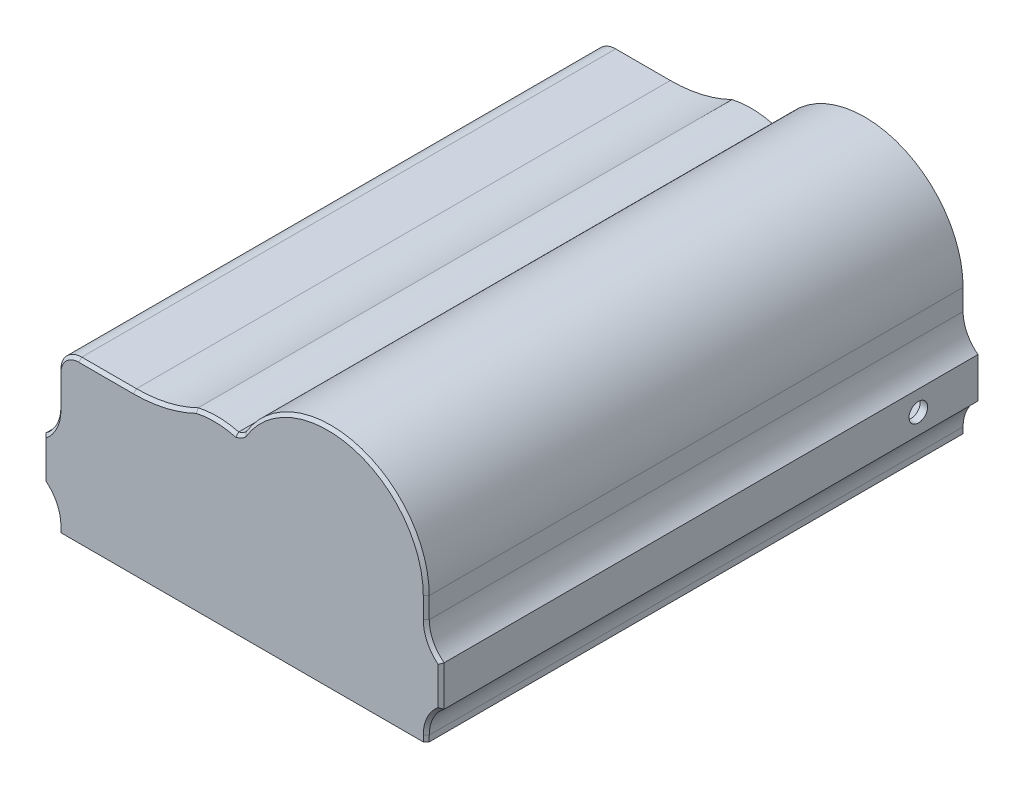
SolidWorks part; units mm, degrees
material "Nylon 6/10"
ref_plane "Front Plane" through (0, 0, 0) normal (0, 0, 1) x (1, 0, 0)
ref_plane "Top Plane" through (0, 0, 0) normal (0, 1, 0) x (1, 0, 0)
ref_plane "Right Plane" through (0, 0, 0) normal (1, 0, 0) x (0, 0, -1)
sketch "Sketch1" plane through (0, 0, -195.5168) normal (0, 0, 1) x (1, 0, 0)
  line L7 (104.3078, -30.7874) -> (104.3078, -41.7094) construction
  line L8 (107.547, -28.7554) -> (106.3398, -28.7554) construction
  line L9 (113.7687, -28.7554) -> (107.547, -28.7554) construction
  line L16 (115.6581, -28.7554) -> (113.7687, -28.7554) construction
  line L17 (163.9978, -41.7094) -> (163.9978, -32.8194) construction
  line L18 (163.9978, -42.9794) -> (163.9978, -41.7094) construction
  line L19 (163.9978, -42.9794) -> (166.5378, -42.9794) construction
  line L20 (166.5378, -42.9794) -> (166.5378, -46.7894) construction
  line L21 (166.5378, -46.7894) -> (163.9978, -46.7894) construction
  line L22 (163.9978, -49.3294) -> (163.9978, -46.7894) construction
  line L23 (163.9978, -49.3294) -> (104.3078, -49.3294) construction
  line L24 (104.3078, -49.3294) -> (104.3078, -46.7894) construction
  line L25 (104.3078, -46.7894) -> (101.7678, -46.7894) construction
  line L26 (101.7678, -46.7894) -> (101.7678, -42.9794) construction
  line L27 (101.7678, -42.9794) -> (104.3078, -42.9794) construction
  line L28 (104.3078, -42.9794) -> (104.3078, -41.7094) construction
  line L29 (104.3078, -30.7874) -> (104.3078, -41.7094) construction
  line L30 (107.547, -28.7554) -> (106.3398, -28.7554) construction
  line L31 (113.7687, -28.7554) -> (107.547, -28.7554) construction
  line L32 (115.6581, -28.7554) -> (113.7687, -28.7554) construction
  line L33 (163.9978, -41.7094) -> (163.9978, -32.8194) construction
  line L35 (163.9978, -42.9794) -> (163.9978, -41.7094) construction
  line L36 (163.9978, -42.9794) -> (166.5378, -42.9794) construction
  line L37 (166.5378, -42.9794) -> (166.5378, -46.7894) construction
  line L38 (166.5378, -46.7894) -> (163.9978, -46.7894) construction
  line L39 (163.9978, -49.3294) -> (163.9978, -46.7894) construction
  line L40 (163.9978, -49.3294) -> (104.3078, -49.3294) construction
  line L41 (104.3078, -49.3294) -> (104.3078, -46.7894) construction
  line L42 (104.3078, -46.7894) -> (101.7678, -46.7894) construction
  line L43 (101.7678, -46.7894) -> (101.7678, -42.9794) construction
  line L44 (101.7678, -42.9794) -> (104.3078, -42.9794) construction
  line L45 (104.3078, -42.9794) -> (104.3078, -41.7094) construction
  line L46 (113.7687, -27.2314) -> (107.547, -27.2314)
  line L47 (107.547, -27.2314) -> (106.3398, -27.2314)
  line L48 (102.7838, -30.7874) -> (102.7838, -41.4554)
  line L49 (102.7838, -41.4554) -> (102.7838, -41.4554)
  line L50 (100.2438, -41.4554) -> (102.7838, -41.4554)
  line L51 (100.2438, -48.3134) -> (100.2438, -41.4554)
  line L52 (102.7838, -48.3134) -> (100.2438, -48.3134)
  line L53 (102.7838, -50.8534) -> (102.7838, -48.3134)
  line L54 (165.5218, -50.8534) -> (102.7838, -50.8534) construction
  line L55 (165.5218, -50.8534) -> (165.5218, -48.3134)
  line L56 (168.0618, -48.3134) -> (165.5218, -48.3134)
  line L57 (168.0618, -41.4554) -> (168.0618, -48.3134)
  line L58 (165.5218, -41.4554) -> (168.0618, -41.4554)
  line L59 (165.5218, -41.4554) -> (165.5218, -41.4554)
  line L60 (165.5218, -41.4554) -> (165.5218, -32.8194)
  line L61 (115.6581, -27.2314) -> (113.7687, -27.2314)
  line L62 (102.7838, -50.8534) -> (102.7838, -54.4094)
  line L63 (102.7838, -54.4094) -> (165.5218, -54.4094)
  line L64 (165.5218, -54.4094) -> (165.5218, -50.8534)
  line L65 (137.4278, -54.4094) -> (143.9318, -54.4094) construction
  line L66 (102.7838, -51.8694) -> (165.5218, -51.8694)
  line L67 (163.9978, -49.3294) -> (163.9978, -51.8694)
  line L68 (104.3078, -49.3294) -> (104.3078, -51.8694)
  arc A0 (106.3398, -28.7554) -> (104.3078, -30.7874) centre (106.3398, -30.7874) ccw construction
  arc A1 (115.6581, -28.7554) -> (126.6696, -26.2444) centre (115.6581, -3.3554) ccw construction
  arc A2 (133.0196, -26.4694) -> (126.6696, -26.2444) centre (129.3953, -39.0384) ccw construction
  arc A3 (133.0196, -26.4694) -> (135.5596, -25.1994) centre (132.2865, -21.8281) ccw construction
  arc A4 (163.9978, -32.8194) -> (135.5596, -25.1994) centre (148.7578, -32.8194) ccw construction
  arc A5 (106.3398, -28.7554) -> (104.3078, -30.7874) centre (106.3398, -30.7874) ccw construction
  arc A6 (115.6581, -28.7554) -> (126.6696, -26.2444) centre (115.6581, -3.3554) ccw construction
  arc A7 (133.0196, -26.4694) -> (126.6696, -26.2444) centre (129.3953, -39.0384) ccw construction
  arc A8 (133.0196, -26.4694) -> (135.5596, -25.1994) centre (132.2865, -21.8281) ccw construction
  arc A9 (163.9978, -32.8194) -> (135.5596, -25.1994) centre (148.7578, -32.8194) ccw construction
  arc A10 (106.3398, -27.2314) -> (102.7838, -30.7874) centre (106.3398, -30.7874) ccw
  arc A15 (165.5218, -32.8194) -> (134.3603, -24.232) centre (148.7578, -32.8194) ccw
  arc A16 (133.0731, -24.904) -> (134.3603, -24.232) centre (132.2865, -21.8281) ccw
  arc A17 (133.0731, -24.904) -> (126.1661, -24.7948) centre (129.3953, -39.0384) ccw
  arc A18 (115.6581, -27.2314) -> (126.1661, -24.7948) centre (115.6581, -3.3554) ccw
  dimension "D1" = 1.524
  dimension "D2" = 2.54
extrude "Boss-Extrude1" add sketch "Sketch1" along normal blind 2.54
sketch "Sketch2" plane through (0, 0, -192.9768) normal (0, 0, 1) x (1, 0, 0)
  line L0 (115.6581, -28.5014) -> (106.3398, -28.5014)
  line L1 (104.0538, -30.7874) -> (104.0538, -42.7254)
  line L2 (104.0538, -42.7254) -> (101.5138, -42.7254)
  line L3 (101.5138, -42.7254) -> (101.5138, -47.0434)
  line L4 (101.5138, -47.0434) -> (104.0538, -47.0434)
  line L5 (104.0538, -47.0434) -> (104.0538, -53.1394)
  line L6 (104.0538, -53.1394) -> (164.2518, -53.1394) construction
  line L7 (164.2518, -53.1394) -> (164.2518, -47.0434)
  line L8 (164.2518, -47.0434) -> (166.7918, -47.0434)
  line L9 (166.7918, -47.0434) -> (166.7918, -42.7254)
  line L10 (166.7918, -42.7254) -> (164.2518, -42.7254)
  line L11 (164.2518, -42.7254) -> (164.2518, -32.8194)
  line L12 (115.6581, -27.2314) -> (106.3398, -27.2314)
  line L13 (102.7838, -30.7874) -> (102.7838, -41.4554)
  line L14 (102.7838, -41.4554) -> (100.2438, -41.4554)
  line L15 (100.2438, -41.4554) -> (100.2438, -48.3134)
  line L16 (100.2438, -48.3134) -> (102.7838, -48.3134)
  line L17 (102.7838, -48.3134) -> (102.7838, -54.4094)
  line L18 (102.7838, -54.4094) -> (165.5218, -54.4094)
  line L19 (165.5218, -54.4094) -> (165.5218, -48.3134)
  line L20 (165.5218, -48.3134) -> (168.0618, -48.3134)
  line L21 (168.0618, -48.3134) -> (168.0618, -41.4554)
  line L22 (168.0618, -41.4554) -> (165.5218, -41.4554)
  line L23 (165.5218, -41.4554) -> (165.5218, -32.8194)
  line L24 (115.6581, -27.2314) -> (106.3398, -27.2314)
  line L25 (102.7838, -30.7874) -> (102.7838, -41.4554)
  line L26 (102.7838, -41.4554) -> (100.2438, -41.4554)
  line L27 (100.2438, -41.4554) -> (100.2438, -48.3134)
  line L28 (100.2438, -48.3134) -> (102.7838, -48.3134)
  line L29 (102.7838, -48.3134) -> (102.7838, -54.4094)
  line L30 (102.7838, -54.4094) -> (165.5218, -54.4094)
  line L31 (165.5218, -54.4094) -> (165.5218, -48.3134)
  line L32 (165.5218, -48.3134) -> (168.0618, -48.3134)
  line L33 (168.0618, -48.3134) -> (168.0618, -41.4554)
  line L34 (168.0618, -41.4554) -> (165.5218, -41.4554)
  line L35 (165.5218, -41.4554) -> (165.5218, -32.8194)
  line L36 (104.0538, -51.8694) -> (164.2518, -51.8694)
  line L52 (102.7838, -54.4094) -> (165.5218, -54.4094) construction
  arc A0 (106.3398, -28.5014) -> (104.0538, -30.7874) centre (106.3398, -30.7874) ccw
  arc A1 (164.2518, -32.8194) -> (135.3577, -25.0413) centre (148.7578, -32.8194) ccw
  arc A2 (133.0347, -26.2095) -> (135.3577, -25.0413) centre (132.2865, -21.8281) ccw
  arc A3 (133.0347, -26.2095) -> (126.5867, -26.0024) centre (129.3953, -39.0384) ccw
  arc A4 (115.6581, -28.5014) -> (126.5867, -26.0024) centre (115.6581, -3.3554) ccw
  arc A5 (115.6581, -27.2314) -> (126.1661, -24.7948) centre (115.6581, -3.3554) ccw
  arc A6 (106.3398, -27.2314) -> (102.7838, -30.7874) centre (106.3398, -30.7874) ccw
  arc A7 (165.5218, -32.8194) -> (134.3603, -24.232) centre (148.7578, -32.8194) ccw
  arc A8 (133.0731, -24.904) -> (134.3603, -24.232) centre (132.2865, -21.8281) ccw
  arc A9 (133.0731, -24.904) -> (126.1661, -24.7948) centre (129.3953, -39.0384) ccw
  arc A10 (115.6581, -27.2314) -> (126.1661, -24.7948) centre (115.6581, -3.3554) ccw
  arc A11 (106.3398, -27.2314) -> (102.7838, -30.7874) centre (106.3398, -30.7874) ccw
  arc A12 (165.5218, -32.8194) -> (134.3603, -24.232) centre (148.7578, -32.8194) ccw
  arc A13 (133.0731, -24.904) -> (134.3603, -24.232) centre (132.2865, -21.8281) ccw
  arc A14 (133.0731, -24.904) -> (126.1661, -24.7948) centre (129.3953, -39.0384) ccw
  arc M150 (126.1661, -24.7948) -> (115.6581, -27.2314) centre (115.6581, -3.3554) cw
  line M151 (115.6581, -27.2314) -> (106.3398, -27.2314)
  arc M152 (106.3398, -27.2314) -> (102.7838, -30.7874) centre (106.3398, -30.7874) ccw
  line M153 (102.7838, -30.7874) -> (102.7838, -41.4554)
  line M154 (102.7838, -41.4554) -> (100.2438, -41.4554)
  line M155 (100.2438, -41.4554) -> (100.2438, -48.3134)
  line M156 (100.2438, -48.3134) -> (102.7838, -48.3134)
  line M157 (102.7838, -48.3134) -> (102.7838, -54.4094)
  line M159 (165.5218, -54.4094) -> (165.5218, -48.3134)
  line M160 (165.5218, -48.3134) -> (168.0618, -48.3134)
  line M161 (168.0618, -48.3134) -> (168.0618, -41.4554)
  line M162 (168.0618, -41.4554) -> (165.5218, -41.4554)
  line M163 (165.5218, -41.4554) -> (165.5218, -32.8194)
  arc M164 (165.5218, -32.8194) -> (134.3603, -24.232) centre (148.7578, -32.8194) ccw
  arc M165 (134.3603, -24.232) -> (133.0731, -24.904) centre (132.2865, -21.8281) cw
  arc M166 (133.0731, -24.904) -> (126.1661, -24.7948) centre (129.3953, -39.0384) ccw
  line M189 (102.7838, -54.4094) -> (165.5218, -54.4094)
  dimension "D1" = 0
  dimension "D3" = 2.54
  dimension "D2" = 1.27
extrude "Boss-Extrude5" add sketch "Sketch2" against normal offset from surface (91.44 mm away) 7.62 contours L0 A4 A3 A2 A1 L11 L10 L9 L8 L7 L36 L5 L4 L3 L2 L1 A0 M156 M157 M189 M159 M160 M161 M162 M163 M164 M165 M166 M150 M151 M152 M153 M154 M155 region at (121.2275, -27.3733, -192.9768) offset beyond the face yes
sketch "Sketch6" plane through (100.2438, 0, 0) normal (-1, 0, 0) x (0, 0, 1)
  circle A0 centre (-274.2568, -44.8844) radius 1.5875
  dimension "D1" = 3.175
extrude "Cut-Extrude1" cut sketch "Sketch6" against normal up to next
sketch "Sketch7" plane through (168.0618, 0, 0) normal (1, 0, 0) x (0, 0, -1)
  circle A0 centre (274.2568, -44.8844) radius 1.5875
  dimension "D1" = 3.175
extrude "Cut-Extrude2" cut sketch "Sketch7" against normal up to next
sketch "Sketch9" plane through (0, 0, -284.4168) normal (0, 0, -1) x (-1, 0, 0)
  line L0 (-164.2518, -51.8694) -> (-104.0538, -51.8694) construction
  line L1 (-159.1718, -51.8694) -> (-109.1338, -51.8694)
  line L2 (-159.1718, -51.8694) -> (-159.1718, -54.4094)
  line L3 (-159.1718, -54.4094) -> (-109.1338, -54.4094)
  line L4 (-109.1338, -51.8694) -> (-109.1338, -54.4094)
  line L5 (-165.5218, -54.4094) -> (-102.7838, -54.4094) construction
  line L6 (-102.7838, -54.4094) -> (-102.7838, -48.3134) construction
  line L7 (-165.5218, -48.3134) -> (-165.5218, -54.4094) construction
  dimension "D1" = 6.35
  dimension "D2" = 6.35
extrude "Cut-Extrude4" cut sketch "Sketch9" against normal offset from surface (72.39 mm away) 19.05 up to face at (131.0677, -38.0913, -192.9768)
fillet "Fillet1" radius 12.7 2 edges at (159.1718, -53.1394, -212.0268) (109.1338, -53.1394, -212.0268)
fillet "Fillet2" radius 6.35 4 edges at (102.7838, -48.3134, -238.6968) (102.7838, -41.4554, -238.6968) (165.5218, -48.3134, -238.6968) (165.5218, -41.4554, -238.6968)
chamfer "Chamfer1" distance 0.508 angle 45 16 edges at (165.5218, -53.9014, -192.9768) (166.1922, -50.5536, -192.9768) (168.0618, -44.8844, -192.9768) (102.7838, -53.9014, -192.9768) (102.1135, -50.5536, -192.9768) (100.2438, -44.8844, -192.9768) (102.1135, -39.2152, -192.9768) (166.1922, -39.2152, -192.9768) (102.7838, -33.5814, -192.9768) (165.5218, -34.5974, -192.9768) (103.8254, -28.2729, -192.9768) (153.2116, -16.6579, -192.9768) (133.7557, -24.6426, -192.9768) (129.6262, -24.4351, -192.9768) (121.0515, -26.6143, -192.9768) (110.999, -27.2314, -192.9768)
